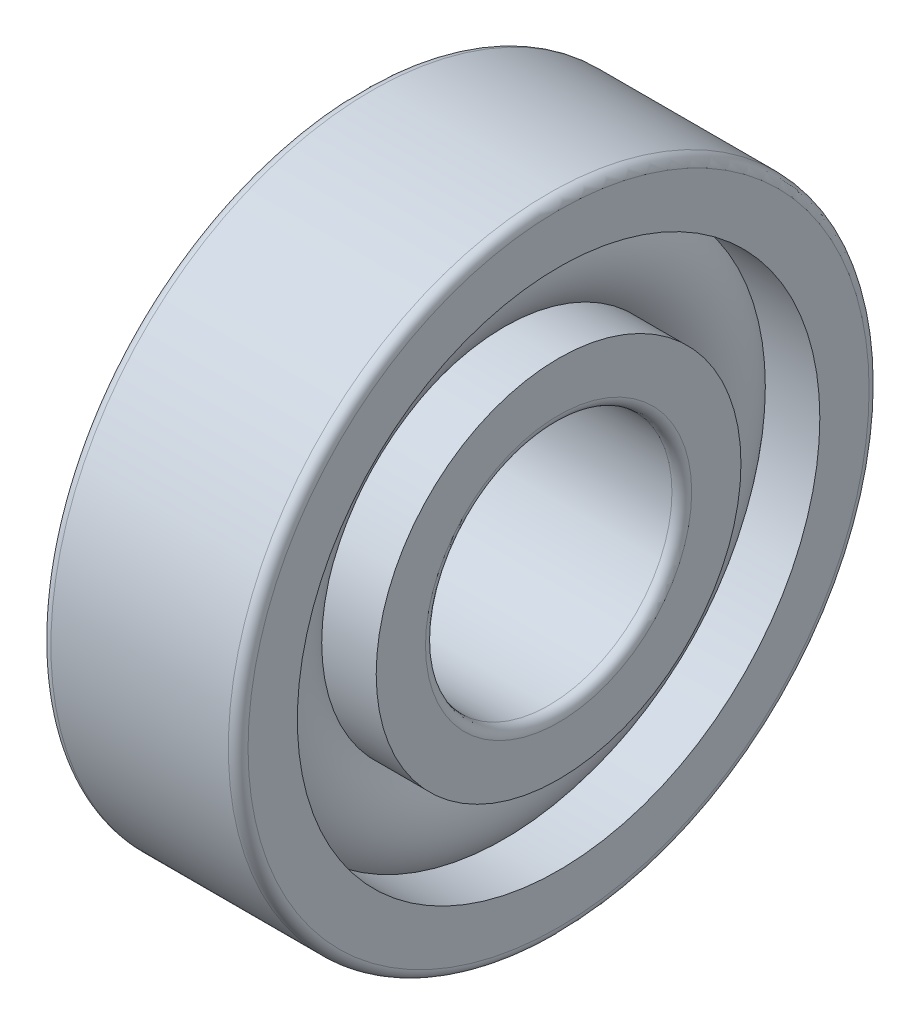
SolidWorks part; units mm, degrees
ref_plane "Plane1" through (0, 0, 0) normal (0, 0, 1) x (1, 0, 0)
ref_plane "Plane2" through (0, 0, 0) normal (0, 1, 0) x (1, 0, 0)
ref_plane "Plane3" through (0, 0, 0) normal (1, 0, 0) x (0, 0, -1)
sketch "Clipboard" plane through (0, 0, 0) normal (0, 0, 1) x (1, 0, 0)
  line L0 (-10, 0) -> (10, 0) construction
  line L1 (0, 0) -> (22.3471, -0.7804)
  line L2 (0, 0) -> (4.4973, 0.157)
  line L3 (0, 0) -> (22.3471, -0.7804)
  line L4 (0, 0) -> (-22.3573, -0.3902)
  dimension "BallCLRad" = 4.5
sketch "CagSpiSke" plane through (0, 0, 0) normal (0, 0, 1) x (1, 0, 0)
  line L0 (0.12, 4.3) -> (0.12, 4.7)
  line L1 (0.12, 4.7) -> (-0.12, 4.7)
  line L2 (-0.12, 4.7) -> (-0.12, 4.3)
  line L3 (-0.12, 4.3) -> (0.12, 4.3)
  line L4 (-20.6375, 0) -> (20.6375, 0) construction
  line L5 (0, 0) -> (0, 23.7692) construction
  dimension "OD" = 9.4
  dimension "ID" = 8.6
revolve "CageSpine" add sketch "CagSpiSke" angle 0.001 about L4 reverse direction yes
ref_axis "Axis1" through (-50, 0, 0) along (1, 0, 0)
sketch "CagBalSke" plane through (0, 0, 0) normal (0, 0, 1) x (1, 0, 0)
  line L0 (-1.32, 4.5) -> (1.32, 4.5)
  line L1 (-1.905, 4.5) -> (1.905, 4.5) construction
  line L2 (-10, 0) -> (10, 0) construction
  line L3 (0, 0) -> (0, 24) construction
  arc A0 (1.32, 4.5) -> (-1.32, 4.5) centre (0, 4.5) cw
  dimension "BallCLRad" = 4.5
revolve "CageBall" [suppressed] add sketch "CagBalSke" angle 360 about L1 reverse direction yes
pattern_circular "CageBalls" [suppressed] count 2 every 180 about axis through (-50, 0, 0) along (1, 0, 0)
sketch "CagTrmODSke" plane through (0, 0, 0) normal (0, 0, 1) x (1, 0, 0)
  line L0 (1.321, 4.7) -> (1.321, 5.821)
  line L1 (1.321, 5.821) -> (-1.321, 5.821)
  line L2 (-1.321, 5.821) -> (-1.321, 4.7)
  line L3 (-1.321, 4.7) -> (1.321, 4.7)
  line L4 (-20.6375, 0) -> (20.6375, 0) construction
  line L5 (0, 0) -> (0, 25) construction
  dimension "Width" = 2.642
  dimension "ID" = 9.4
  dimension "OD" = 11.642
revolve "CageTrimOD" [suppressed] cut sketch "CagTrmODSke" angle 360 about L4 reverse direction yes
sketch "CagTrmIDSke" plane through (0, 0, 0) normal (0, 0, 1) x (1, 0, 0)
  line L0 (1.321, 3.181) -> (1.321, 4.3)
  line L1 (1.321, 4.3) -> (-1.321, 4.3)
  line L2 (-1.321, 4.3) -> (-1.321, 3.181)
  line L3 (-1.321, 3.181) -> (1.321, 3.181)
  line L4 (-20.6375, 0) -> (20.6375, 0) construction
  line L5 (0, 0) -> (0, 25) construction
  dimension "Width" = 2.642
  dimension "ID" = 6.362
  dimension "OD" = 8.6
revolve "CageTrimID" [suppressed] cut sketch "CagTrmIDSke" angle 360 about L4 reverse direction yes
sketch "BalSimSke" plane through (0, 0, 0) normal (0, 0, 1) x (1, 0, 0)
  line L0 (-10, 0) -> (10, 0) construction
  line L1 (-10, 4.5) -> (10, 4.5) construction
  line L2 (0, 0) -> (0, 23) construction
  circle A0 centre (0, 4.5) radius 1.2
  dimension "BallCLRad" = 4.5
  dimension "Ball_diameter" = 2.4
revolve "BallsSimplified" add sketch "BalSimSke" angle 360 about L0
sketch "BalDetSke" plane through (0, 0, 0) normal (0, 0, 1) x (1, 0, 0)
  line L0 (-1.2, 4.5) -> (1.2, 4.5)
  line L1 (-1.905, 4.5) -> (1.905, 4.5) construction
  line L2 (0, 0) -> (0, 25) construction
  arc A0 (1.2, 4.5) -> (-1.2, 4.5) centre (0, 4.5) cw
  dimension "BallCLRad" = 4.5
  dimension "Ball_diameter" = 2.4
revolve "BallDetailed" [suppressed] add sketch "BalDetSke" angle 360 about L1 reverse direction yes
sketch "InnRacSke" plane through (0, 0, 0) normal (0, 0, 1) x (1, 0, 0)
  line L0 (-0.8606, 3.7) -> (-2, 3.7)
  line L1 (-2, 3.7) -> (-2, 2.7)
  line L2 (-1.8, 2.5) -> (1.8, 2.5)
  line L3 (2, 2.7) -> (2, 3.7)
  line L4 (2, 3.7) -> (0.8606, 3.7)
  line L5 (-20.6375, 0) -> (20.6375, 0) construction
  line L6 (0, 0) -> (0, 30) construction
  arc A0 (-2, 2.7) -> (-1.8, 2.5) centre (-1.8, 2.7) ccw
  arc A1 (1.8, 2.5) -> (2, 2.7) centre (1.8, 2.7) ccw
  arc A2 (0.8606, 3.7) -> (-0.8606, 3.7) centre (0, 4.5) cw
  dimension "BallCLRad" = 4.5
  dimension "Fillet_radius" = 0.2
  dimension "Ball_diameter" = 2.35
  dimension "ID" = 5
  dimension "OD" = 7.4
  dimension "Width" = 4
revolve "InnerRace" add sketch "InnRacSke" angle 360 about L5 reverse direction yes
sketch "OutRacSke" plane through (0, 0, 0) normal (0, 0, 1) x (1, 0, 0)
  line L0 (-0.8606, 5.3) -> (-2, 5.3)
  line L1 (-2, 5.3) -> (-2, 6.3)
  line L2 (-1.8, 6.5) -> (1.8, 6.5)
  line L3 (2, 6.3) -> (2, 5.3)
  line L4 (2, 5.3) -> (0.8606, 5.3)
  line L5 (-20.6375, 0) -> (20.6375, 0) construction
  line L6 (0, 0) -> (0, 30) construction
  arc A0 (-2, 6.3) -> (-1.8, 6.5) centre (-1.8, 6.3) cw
  arc A1 (1.8, 6.5) -> (2, 6.3) centre (1.8, 6.3) cw
  arc A2 (0.8606, 5.3) -> (-0.8606, 5.3) centre (0, 4.5) ccw
  dimension "BallCLRad" = 4.5
  dimension "Fillet_radius" = 0.2
  dimension "Ball_diameter" = 2.35
  dimension "Width" = 4
revolve "OuterRace" add sketch "OutRacSke" angle 360 about L5 reverse direction yes
pattern_circular "BallsDetailed" [suppressed] count 2 every 180 about axis through (-50, 0, 0) along (1, 0, 0)
equation "\"BallCLRad@Clipboard\" = ( \"OD@OutRacSke\" + \"ID@InnRacSke\" ) / 4"
equation "\"BallCLRad@BalSimSke\" = \"BallCLRad@Clipboard\""
equation "\"BallCLRad@BalDetSke\" = \"BallCLRad@Clipboard\""
equation "\"BallCLRad@InnRacSke\" = \"BallCLRad@Clipboard\""
equation "\"BallCLRad@OutRacSke\" = \"BallCLRad@Clipboard\""
equation "\"Ball_diameter@InnRacSke\" = \"Ball_diameter@BalDetSke\" - 0.05"
equation "\"Ball_diameter@OutRacSke\" = \"Ball_diameter@BalDetSke\" - 0.05"
equation "\"Ball_diameter@BalSimSke\" = \"Ball_diameter@BalDetSke\""
equation "\"Width@OutRacSke\" = \"Width@InnRacSke\""
equation "\"Fillet_radius@OutRacSke\" = \"Fillet_radius@InnRacSke\""
equation "\"Max_count@Clipboard\" = int( 3.14159265 / atn(( \"Ball_diameter@BalDetSke\" / 2) / sqr( \"BallCLRad@Clipboard\"  *  \"BallCLRad@Clipboard\" - ( \"Ball_diameter@BalDetSke\" / 2) *  ( \"Ball_diameter@BalDetSke\" / 2))))"
equation "\"Max_count@Clipboard\" = ((sgn( \"Max_count@Clipboard\" - \"Count@Clipboard\" )-1)*( \"Max_count@Clipboard\" - \"Count@Clipboard\" ))/-2+ \"Count@Clipboard\""
equation "\"Count@BallsDetailed\" = int( \"Show_count@Clipboard\" ) "
equation "\"Count@BallsDetailed\" = ((sgn( \"Count@BallsDetailed\" - \"Max_count@Clipboard\" )-1)*( \"Count@BallsDetailed\" - \"Max_count@Clipboard\" ))/-2+ \"Max_count@Clipboard\""
equation "\"Count@BallsDetailed\" = ((sgn( \"Count@BallsDetailed\" - \"Min_count@Clipboard\" )+1)*( \"Count@BallsDetailed\" - \"Min_count@Clipboard\"))/2 +\"Min_count@Clipboard\""
equation "\"Angle@BallsDetailed\" = 360.0 / \"Max_count@Clipboard\""
equation "\"BallCLRad@CagBalSke\" = \"BallCLRad@Clipboard\""
equation "\"Count@CageBalls\" = \"Count@BallsDetailed\""
equation "\"Angle@CageBalls\" = \"Angle@BallsDetailed\""
equation "\"Angle@CageSpine\" =  \"Angle@CageBalls\" * ( \"Count@CageBalls\" -1 + int( \"Count@CageBalls\" / \"Max_count@Clipboard\" ) )  + 0.001 -  int( \"Count@CageBalls\" / \"Max_count@Clipboard\" ) * 0.001"
equation "\"Angle@CageSpine\" =  \"Angle@CageSpine\" * int( \"Min_count@Clipboard\" / 2) + int(1 / \"Min_count@Clipboard\")  * 0.001"
equation "\"CageWallOD@CagBalSke\" =  \"Ball_diameter@BalDetSke\" * 1.1"
equation "\"Thickness@CagSpiSke\" =  \"Ball_diameter@BalDetSke\" * 0.1"
equation "\"OD@CagTrmODSke\" = \"BallCLRad@Clipboard\" * 2 + \"CageWallOD@CagBalSke\" + 0.002"
equation "\"ID@CagTrmODSke\" = \"BallCLRad@Clipboard\" * 2 + \"Ball_diameter@BalDetSke\" / 6"
equation "\"OD@CagTrmIDSke\" = \"BallCLRad@Clipboard\" * 2 - \"Ball_diameter@BalDetSke\" / 6"
equation "\"ID@CagTrmIDSke\" = \"BallCLRad@Clipboard\" * 2 - \"CageWallOD@CagBalSke\" + 0.002"
equation "\"OD@CagSpiSke\" = \"ID@CagTrmODSke\""
equation "\"ID@CagSpiSke\" = \"OD@CagTrmIDSke\""
equation "\"Width@CagTrmODSke\" = \"CageWallOD@CagBalSke\" + 0.002"
equation "\"Width@CagTrmIDSke\" = \"CageWallOD@CagBalSke\" + 0.002"
